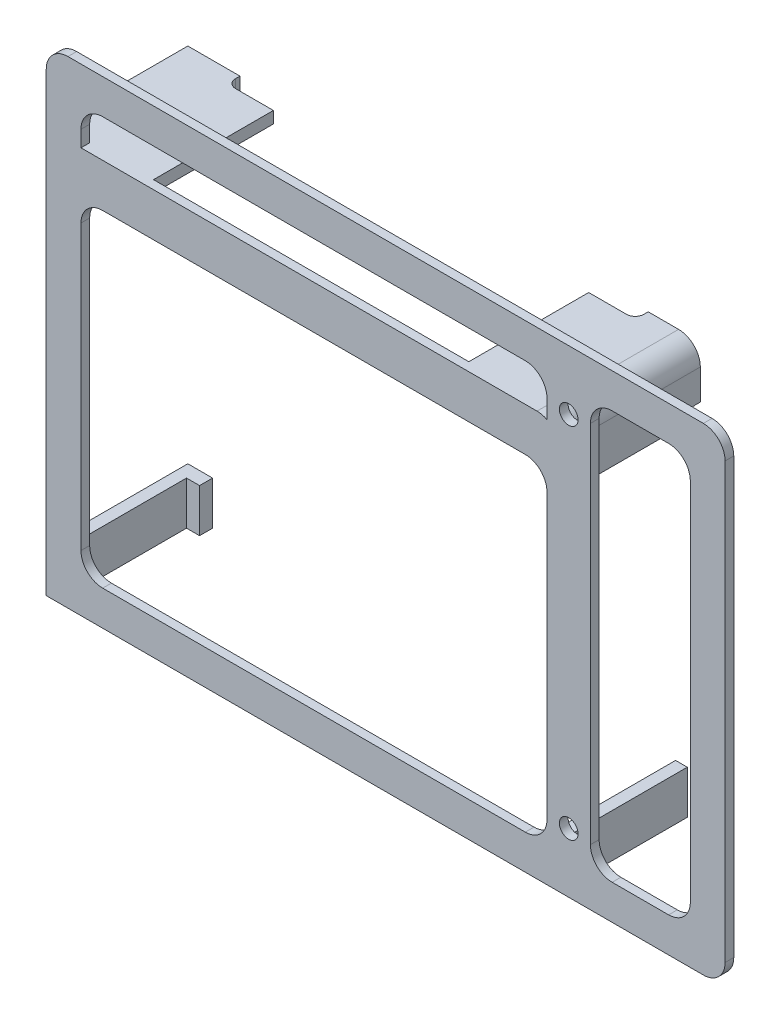
SolidWorks part; units mm, degrees
ref_plane "Front Plane" through (0, 0, 0) normal (0, 0, 1) x (1, 0, 0)
ref_plane "Top Plane" through (0, 0, 0) normal (0, 1, 0) x (1, 0, 0)
ref_plane "Right Plane" through (0, 0, 0) normal (1, 0, 0) x (0, 0, -1)
sketch "Sketch1" plane through (0, 0, 0) normal (0, 0, 1) x (1, 0, 0)
  line L0 (115.3, 20) -> (125.3, 20) construction
  line L1 (0, 0) -> (156.3, 0)
  line L2 (0, 0) -> (0, 110)
  line L3 (0, 110) -> (156.3, 110)
  line L4 (156.3, 0) -> (156.3, 110)
  line L5 (8, 8) -> (115.3, 8)
  line L6 (8, 8) -> (8, 83.3)
  line L7 (8, 102) -> (115.3, 102)
  line L8 (148.3, 8) -> (148.3, 102)
  line L9 (115.3, 83.3) -> (115.3, 8)
  line L10 (8, 83.3) -> (115.3, 83.3)
  line L11 (115.3, 102) -> (115.3, 93.3)
  line L13 (125.3, 8) -> (125.3, 102)
  line L14 (125.3, 102) -> (148.3, 102)
  line L15 (125.3, 8) -> (148.3, 8)
  line L16 (148.3, 102) -> (156.3, 102) construction
  line L17 (8, 93.3) -> (115.3, 93.3)
  line L18 (8, 93.3) -> (8, 102)
  point P4 (120.3, 20)
  point P21 (0, 0)
  point P22 (0, 0)
  point P23 (0, 0)
  point P24 (0, 0)
  point P25 (0, 0)
  dimension "D1" = 110
  dimension "D2" = 10
  dimension "D3" = 8
  dimension "D4" = 8
  dimension "D5" = 8
  dimension "D6" = 8
  dimension "D7" = 36
  dimension "D8" = 10
  dimension "D9" = 115.3
  dimension "D10" = 18.7
  dimension "D11" = 20
extrude "Boss-Extrude1" add sketch "Sketch1" along normal blind 2
hole_wizard "#6 Clearance Hole1" positions "Sketch4" profile "Sketch5" hole size "#6" standard "ANSI Inch" end condition through all
sketch "Sketch4" plane through (0, 0, 0) normal (0, 0, -1) x (-1, 0, 0)
  line L9 (-120.3, 13.725) -> (-120.3, 96.275) construction
  line L11 (-115.3, 8) -> (-125.3, 8) construction
  line L13 (-156.3, 0) -> (-156.3, 110) construction
  point P0 (-120.3, 13.725)
  point P2 (-120.3, 96.275)
  point P50 (0, 0)
  point P51 (-120.3, 8)
  point P52 (-120.3, 103.9907)
  point P53 (-120.3, 55)
  point P56 (-156.3, 55)
  dimension "D1" = 82.55
sketch "Sketch5" plane through (120.3, 13.725, 0) normal (1, 0, 0) x (0, 1, 0)
  line L0 (0, 0) -> (0, 2)
  line L1 (0, 2) -> (2.1526, 2)
  line L2 (2.1526, 2) -> (2.1526, 0)
  line L5 (2.1526, 0) -> (0, 0)
  line L11 (0, -6.35) -> (0, 107.95) construction
  dimension "Thru Hole Dia." = 4.3053
  dimension "Thru Hole Depth" = 2
sketch "Sketch6" plane through (0, 0, 0) normal (0, 0, -1) x (-1, 0, 0)
  line L0 (0, 0) -> (-156.3, 0) construction
  line L3 (0, 0) -> (-2.7, 0)
  line L4 (0, 0) -> (0, 10)
  line L5 (0, 10) -> (-2.7, 10)
  line L6 (-2.7, 0) -> (-2.7, 10)
  line L7 (-115.3, 0) -> (-118, 0)
  line L8 (-115.3, 0) -> (-115.3, 10)
  line L9 (-115.3, 10) -> (-118, 10)
  line L10 (-118, 0) -> (-118, 10)
  line L11 (0, 81.3) -> (0, 93.3)
  line L13 (0, 110) -> (0, 0) construction
  line L14 (0, 93.3) -> (-22.7, 93.3)
  line L16 (-22.7, 93.3) -> (-22.7, 90.6)
  line L17 (-22.7, 90.6) -> (-2.7, 90.6)
  line L19 (-2.7, 90.6) -> (-2.7, 81.3)
  line L20 (-2.7, 81.3) -> (0, 81.3)
  line L21 (-95.3, 93.3) -> (-118, 93.3)
  line L22 (-118, 93.3) -> (-118, 78.6)
  line L24 (-118, 78.6) -> (-115.3, 78.6)
  line L25 (-115.3, 8) -> (-115.3, 83.3) construction
  line L26 (-115.3, 78.6) -> (-115.3, 90.6)
  line L27 (-115.3, 90.6) -> (-95.3, 90.6)
  line L28 (-95.3, 90.6) -> (-95.3, 93.3)
  dimension "D1" = 10
  dimension "D2" = 2.7
  dimension "D3" = 2.7
  dimension "D4" = 2.7
  dimension "D5" = 20
  dimension "D6" = 90.6
  dimension "D7" = 12
  dimension "D8" = 90.6
  dimension "D9" = 2.7
  dimension "D10" = 20
  dimension "D11" = 12
  dimension "D12" = 10
  dimension "D13" = 2.7
extrude "Boss-Extrude2" add sketch "Sketch6" along normal blind 27.6
sketch "Sketch7" plane through (0, 0, -27.6) normal (0, 0, -1) x (-1, 0, 0)
  line L1 (-115.3, 78.6) -> (-115.3, 90.6) construction
  line L2 (0, 93.3) -> (0, 81.3)
  line L3 (-115.3, 90.6) -> (-95.3, 90.6) construction
  line L4 (0, 0) -> (-5.7, 0)
  line L5 (0, 0) -> (0, 10)
  line L6 (0, 10) -> (-5.7, 10)
  line L7 (-5.7, 0) -> (-5.7, 10)
  line L8 (0, 81.3) -> (-5.7, 81.3)
  line L9 (-5.7, 81.3) -> (-5.7, 87.6)
  line L10 (-5.7, 87.6) -> (-12, 87.6)
  line L11 (-12, 87.6) -> (-12, 93.3)
  line L12 (-22.7, 90.6) -> (-2.7, 90.6) construction
  line L13 (0, 93.3) -> (-8, 93.3) construction
  line L17 (-12, 93.3) -> (0, 93.3)
  line L18 (-118, 93.3) -> (-118, 81.3)
  line L22 (-118, 93.3) -> (-118, 78.6) construction
  line L23 (-118, 81.3) -> (-112.3, 81.3)
  line L24 (-112.3, 81.3) -> (-112.3, 87.6)
  line L25 (-112.3, 87.6) -> (-106, 87.6)
  line L26 (-106, 87.6) -> (-106, 93.3)
  line L27 (-95.3, 93.3) -> (-22.7, 93.3) construction
  line L28 (-106, 93.3) -> (-118, 93.3)
  line L29 (-2.7, 10) -> (-2.7, 0) construction
  line L30 (-2.7, 90.6) -> (-2.7, 81.3) construction
  dimension "D1" = 10
  dimension "D2" = 3
  dimension "D3" = 3
  dimension "D4" = 3
  dimension "D5" = 3
  dimension "D6" = 12
  dimension "D7" = 12
  dimension "D8" = 3
  dimension "D9" = 12
extrude "Boss-Extrude3" add sketch "Sketch7" along normal blind 3
fillet "Fillet3" radius 5 1 edges at (118, 93.3, -15.3)
fillet "Fillet4" radius 2 3 edges at (116.65, 81.3, -27.6) (106, 91.95, -27.6) (12, 91.95, -27.6)
fillet "Fillet5" radius 5 13 edges at (115.3, 8, 1) (8, 8, 1) (8, 83.3, 1) (115.3, 83.3, 1) (125.3, 8, 1) (148.3, 8, 1) (148.3, 102, 1) (115.3, 102, 1) (125.3, 102, 1) (8, 102, 1) (156.3, 0, 1) (156.3, 110, 1) (0, 110, 1)
